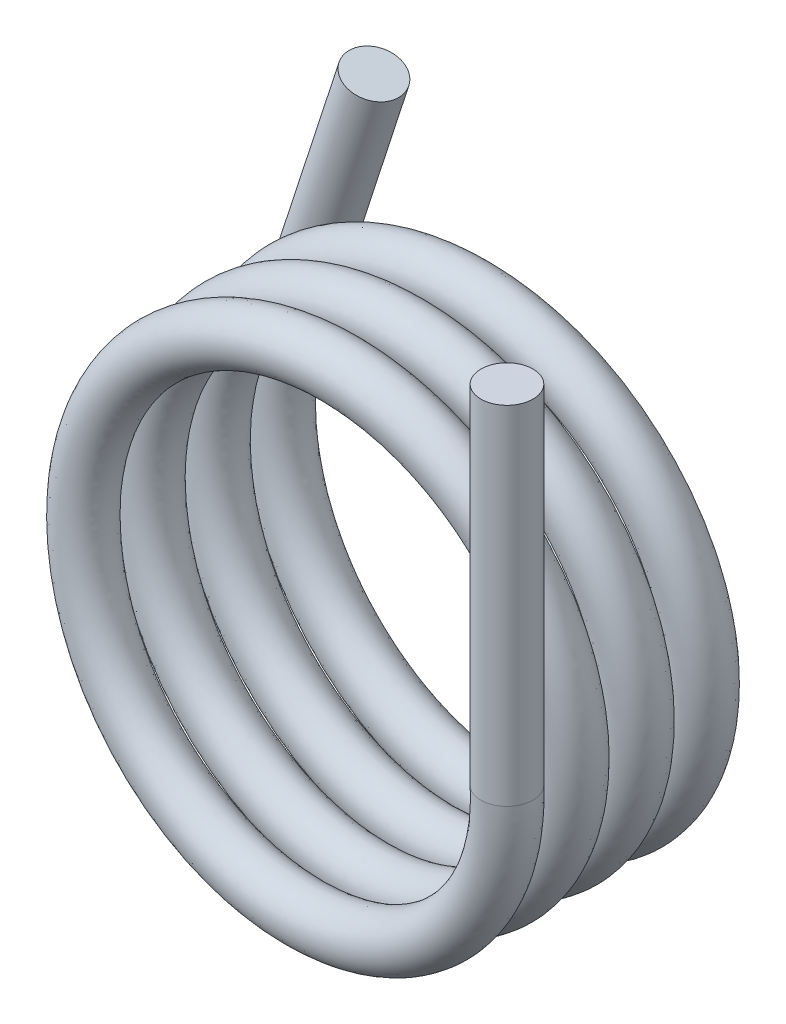
SolidWorks part; units mm, degrees
note: '?' marks a value the reader was unsure of.
ref_plane "Front" through (0, 0, 0) normal (0, 0, 1) x (1, 0, 0)
ref_plane "Top" through (0, 0, 0) normal (0, 1, 0) x (1, 0, 0)
ref_plane "Right" through (0, 0, 0) normal (1, 0, 0) x (0, 0, -1)
sketch "Sketch1" plane through (0, 0, 0) normal (0, 0, 1) x (1, 0, 0)
  circle A0 centre (0, 0) radius 2.625
  circle A1 centre (0, 0) radius 2.25 construction
  circle A2 centre (0, 2.625) radius 0.375 construction
  dimension "D1" = 0.75
  dimension "D2" = 4.5
curve "Helix/Spiral1" pitch 0.75 height 2.6625 turns 3.55
sketch "Sketch2" plane through (0, 0, 0) normal (0, 1, 0) x (1, 0, 0)
  circle A0 centre (2.625, 0) radius 0.3
  dimension "D1" = 0.6
sweep "Sweep1" add profiles "Sketch2" path "Helix/Spiral1"
sketch "Sketch4" plane through (0, 0, 0) normal (0.309, 0.9511, 0) x (-0.9511, 0.309, 0)
  circle A7 centre (2.625, -2.6623) radius 0.3
  circle A11 centre (2.625, -2.6623) radius 0.3
  dimension "D1" = 0
extrude "Boss-Extrude1" add sketch "Sketch4" along normal blind 3
sketch "Sketch5" plane through (0, 0, 0) normal (0, 1, 0) x (1, 0, 0)
  circle A5 centre (2.625, 0) radius 0.3
  circle A9 centre (2.625, 0) radius 0.3
  dimension "D1" = 0
extrude "Boss-Extrude2" add sketch "Sketch5" along normal blind 4
sketch "Sketch11" plane through (0, 0, 0) normal (1, 0, 0) x (0, 0, -1)
  line L0 (0, 0) -> (3.112, 0)
  line L2 (1.556, 0) -> (1.556, 5.2574)
  line L3 (3.112, -2.063) -> (3.112, 0) construction
ref_plane "Plane1" through (0, 0, -1.556) normal (0, 0, 1) x (1, 0, 0)
ref_axis "Axis1" through (2.625, 4, 0) along (0, -1, 0)?
ref_axis "Axis2" through (-1.515, 3.8321, -2.6623) along (-0.309, -0.9511, 0)?
ref_plane "Plane2" through (0, 0, -1.556) normal (0, 0, 1) x (1, 0, 0)
